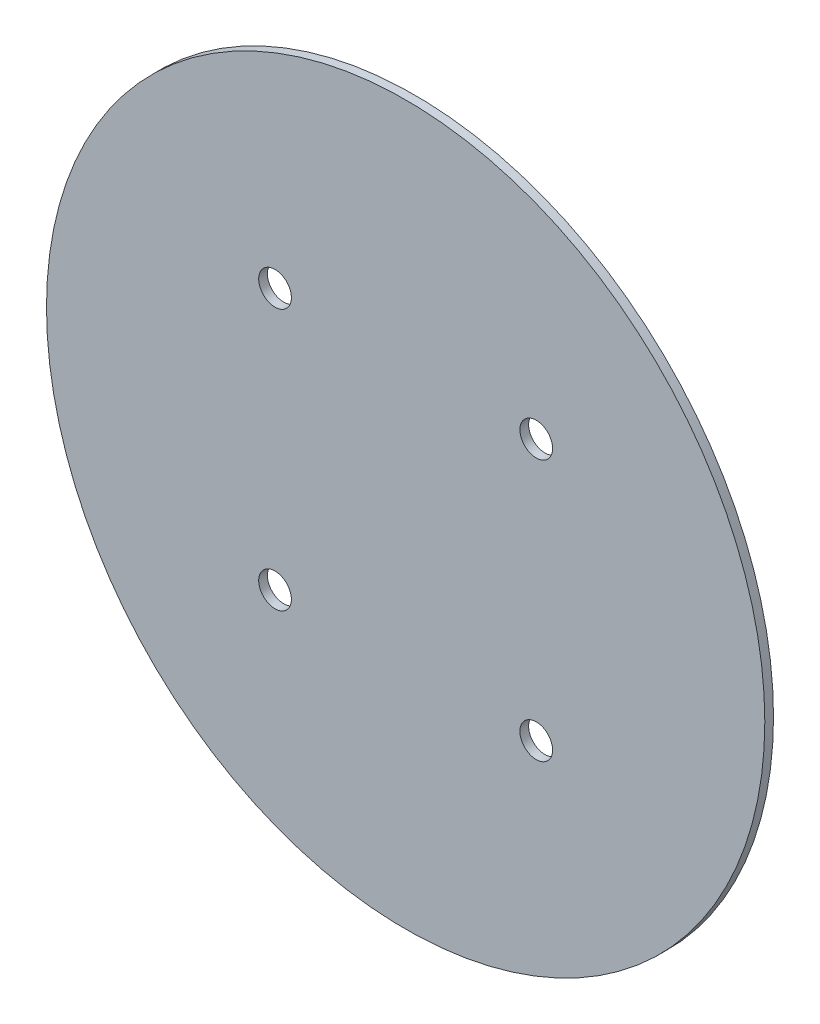
SolidWorks part; units mm, degrees
material "1060 合金"
ref_plane "前视基准面" through (0, 0, 0) normal (0, 0, 1) x (1, 0, 0)
ref_plane "上视基准面" through (0, 0, 0) normal (0, 1, 0) x (1, 0, 0)
ref_plane "右视基准面" through (0, 0, 0) normal (1, 0, 0) x (0, 0, -1)
sketch "草图1" plane through (0, 0, 0) normal (0, 0, 1) x (1, 0, 0)
  circle A0 centre (0, 0) radius 82.5
  dimension "D1" = 165
extrude "凸台-拉伸1" add sketch "草图1" along normal blind 2
sketch "草图2" plane through (0, 0, 2) normal (0, 0, 1) x (1, 0, 0)
  line L0 (0, 30) -> (0, 0) construction
  line L1 (0, 0) -> (0, -30) construction
  line L2 (-34, 0) -> (0, 0) construction
  line L3 (0, 0) -> (30, 0) construction
  circle A4 centre (30, 30) radius 3.755
  circle A5 centre (-30, 30) radius 3.755
  circle A6 centre (-30, -30) radius 3.755
  circle A7 centre (30, -30) radius 3.755
  dimension "D1" = 7.51
  dimension "D2" = 7.51
  dimension "D3" = 7.51
  dimension "D4" = 7.51
  dimension "D5" = 60
  dimension "D6" = 60
extrude "切除-拉伸1" cut sketch "草图2" against normal through all
